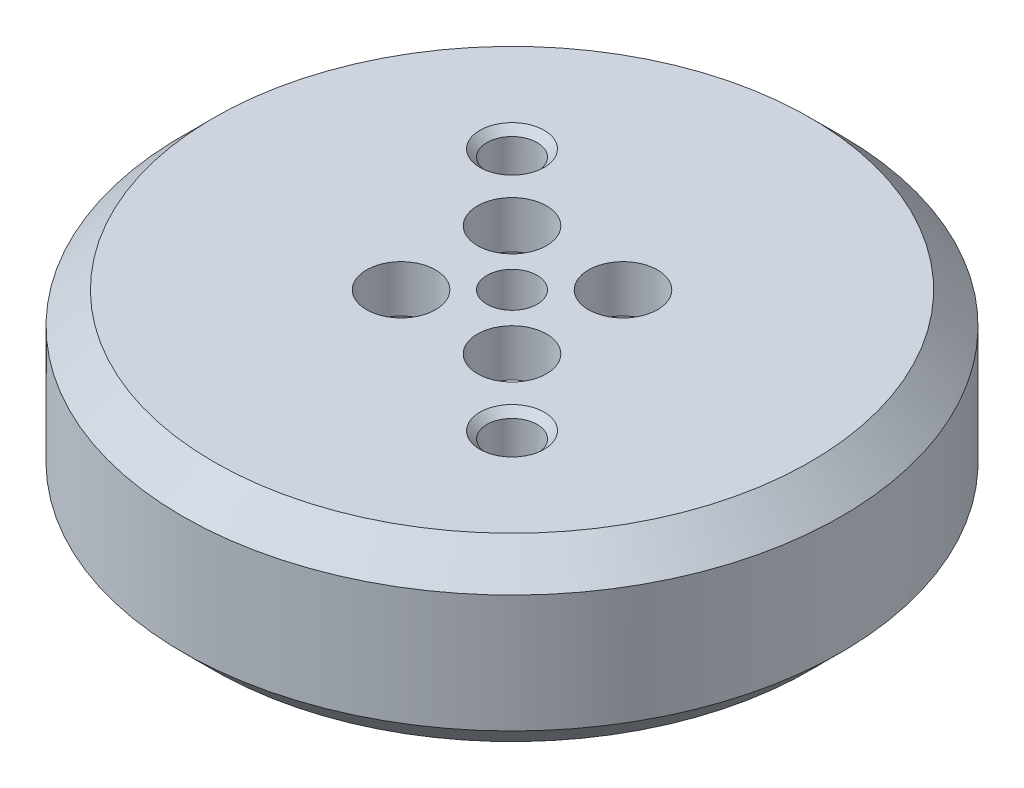
SolidWorks part; units mm, degrees
ref_plane "Front Plane" through (0, 0, 0) normal (0, 0, 1) x (1, 0, 0)
ref_plane "Top Plane" through (0, 0, 0) normal (0, 1, 0) x (1, 0, 0)
ref_plane "Right Plane" through (0, 0, 0) normal (1, 0, 0) x (0, 0, -1)
sketch "Sketch1" plane through (0, 0, 0) normal (0, 1, 0) x (1, 0, 0)
  circle A0 centre (0, 0) radius 10.5
  dimension "D1" = 21
extrude "Boss-Extrude1" add sketch "Sketch1" along normal blind 1.5
sketch "Sketch2" plane through (0, 1.5, 0) normal (0, 1, 0) x (1, 0, 0)
  circle A0 centre (0, 0) radius 0.8
  dimension "D1" = 1.6
extrude "Cut-Extrude1" cut sketch "Sketch2" against normal through all both and the other way through all
hole_wizard "M2 Clearance Hole1" positions "Sketch3" profile "Sketch4" hole size "M2" standard "ANSI Metric"
sketch "Sketch3" plane through (0, 1.5, 0) normal (0, 1, 0) x (1, 0, 0)
  line L1 (-1.7678, 1.7678) -> (1.7678, 1.7678)
  line L2 (-1.7678, 1.7678) -> (-1.7678, -1.7678)
  line L3 (-1.7678, -1.7678) -> (1.7678, -1.7678)
  line L4 (1.7678, 1.7678) -> (1.7678, -1.7678)
  line L5 (-1.7678, 1.7678) -> (1.7678, -1.7678) construction
  point P0 (-1.7678, 1.7678)
  point P2 (1.7678, 1.7678)
  point P4 (1.7678, -1.7678)
  point P6 (-1.7678, -1.7678)
  point P120 (0, 0)
  dimension "D1" = 5
sketch "Sketch4" plane through (-1.7678, 1.5, -1.7678) normal (1, 0, 0) x (0, 0, 1)
  line L0 (0, 0) -> (0, 5.6609)
  line L1 (0, 5.6609) -> (1.1, 5)
  line L2 (1.1, 5) -> (1.1, 0)
  line L5 (1.1, 0) -> (0, 0)
  line L10 (0, 5.6609) -> (-1.1, 5) construction
  line L11 (0, -6.35) -> (0, 107.95) construction
  dimension "Hole Dia." = 2.2
  dimension "Hole Depth" = 5
  dimension "Drill Angle" = 118
sketch "Sketch6" plane through (0, 0, 0) normal (0, 0, 1) x (1, 0, 0)
  line L0 (-10.5, 0) -> (-10.5, -1.25)
  line L1 (-10.5, -1.25) -> (-7.2, -1.25)
  line L2 (-7.2, -1.25) -> (-5, 0)
  line L3 (-5, 0) -> (-10.5, 0)
  line L4 (0, 0) -> (0, -5.6432) construction
  dimension "D1" = 1.25
  dimension "D2" = 5
  dimension "D3" = 7.2
revolve "Revolve1" add sketch "Sketch6" angle 360 about L4
sketch "Sketch7" plane through (0, -1.25, 0) normal (0, -1, 0) x (1, 0, 0)
  circle A0 centre (0, 0) radius 7.2 construction
  circle A1 centre (0, 0) radius 10.5
  circle A2 centre (0, 0) radius 10.5
  circle A3 centre (0, 0) radius 7.2
  dimension "D1" = 0
extrude "Boss-Extrude2" add sketch "Sketch7" along normal blind 3
fillet "Fillet1" radius 1 2 edges at (0, 0, 5) (0, -1.25, 7.2)
chamfer "Chamfer1" distance 1 angle 45 1 edges at (0, 1.5, 10.5)
chamfer "Chamfer2" distance 1 angle 45 1 edges at (0, -4.25, -10.5)
hole_wizard "M2x0.4 Tapped Hole1" positions "Sketch8" profile "Sketch9" tap size "M2x0.4" standard "ANSI Metric"
sketch "Sketch8" plane through (0, 1.5, 0) normal (0, 1, 0) x (1, 0, 0)
  line L0 (-3.8891, 3.8891) -> (3.8891, -3.8891) construction
  circle A1 centre (-1.7678, 1.7678) radius 1.1 construction
  point P0 (-3.8891, 3.8891)
  point P2 (3.8891, -3.8891)
  point P12 (-1.7678, 1.7678)
  point P15 (0, 0)
  dimension "D1" = 11
sketch "Sketch9" plane through (-3.8891, 1.5, -3.8891) normal (1, 0, 0) x (0, 0, 1)
  line L0 (0, 0) -> (0, 5.6807)
  line L1 (0, 5.6807) -> (0.8, 5.2)
  line L2 (0.8, 5.2) -> (0.8, 0.225)
  line L3 (0.8, 0.225) -> (1.025, 0)
  line L5 (1.025, 0) -> (0, 0)
  line L6 (-0.8, 0.225) -> (-1.025, 0) construction
  line L10 (0, 5.6807) -> (-0.8, 5.2) construction
  line L11 (0, -6.35) -> (0, 107.95) construction
  dimension "Tap Drill Dia." = 1.6
  dimension "Tap Drill Depth" = 5.2
  dimension "Near C'Sink Dia." = 2.05
  dimension "Near C'Sink Angle" = 90
  dimension "Drill Angle" = 118
cosmetic thread "Hole Thread1"
cosmetic thread "Hole Thread2"
